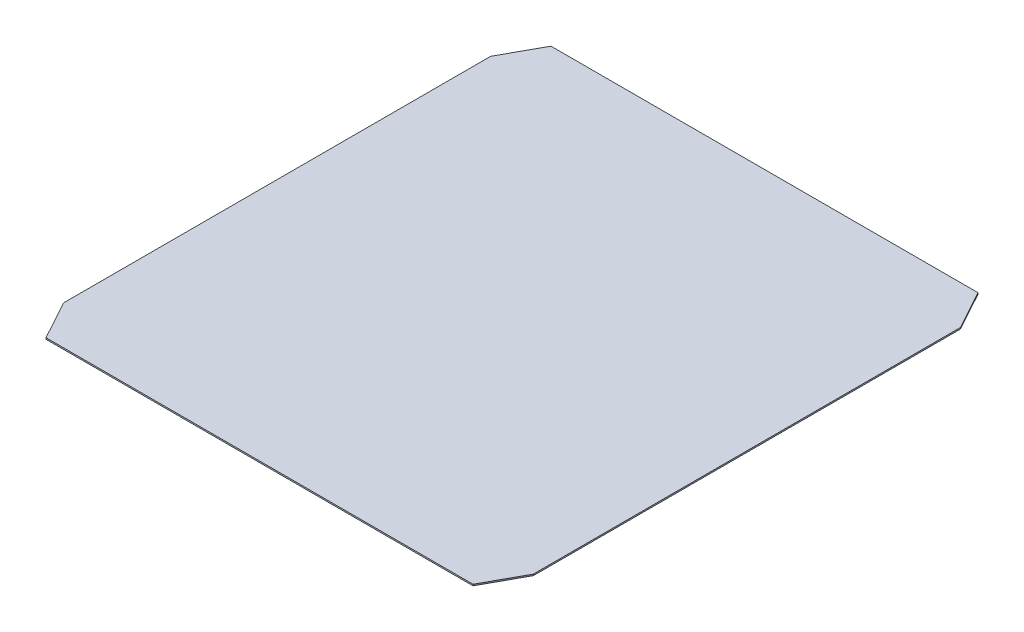
SolidWorks part; units mm, degrees
material "AISI 1020"
ref_plane "Спереди" through (0, 0, 0) normal (0, 0, 1) x (1, 0, 0)
ref_plane "Сверху" through (0, 0, 0) normal (0, 1, 0) x (1, 0, 0)
ref_plane "Справа" through (0, 0, 0) normal (1, 0, 0) x (0, 0, -1)
sketch "Эскиз1" plane through (0, 0, 0) normal (0, 1, 0) x (1, 0, 0)
  line L4 (0, -1000) -> (0, 49000) construction
  line L5 (-1000, 0) -> (49000, 0) construction
  line L6 (-500.5, 455) -> (-455, 538)
  line L7 (500.5, 455) -> (455, 538)
  line L8 (500.5, -538) -> (500.5, 538)
  line L9 (-500.5, -538) -> (500.5, -538)
  line L10 (-500.5, 538) -> (-500.5, -538)
  line L11 (500.5, 538) -> (-500.5, 538)
  line L12 (500.5, -455) -> (500.5, 455)
  line L13 (-455, -538) -> (455, -538)
  line L14 (-500.5, 455) -> (-500.5, -455)
  line L15 (455, 538) -> (-455, 538)
  line L16 (500.5, -455) -> (455, -538)
  line L17 (-500.5, -455) -> (-455, -538)
  dimension "D2" = 5
  dimension "D3" = 5
  dimension "D1" = 2
base flange "Базовая кромка1" sketch "Эскиз1" thickness 3 reverse thickness direction no parameters "D1"=0.75
sketch "Сгиб-Линии1" plane through (0, 0, 0) normal (0, 1, 0) x (1, 0, 0)
sketch "Граничная рамка1" plane through (0, 0, 0) normal (0, 1, 0) x (1, 0, 0)
sheet metal parameters "Листовой металл3" thickness 3 parameters "D1"=0.75
flat pattern "Развертка3" [suppressed]
sketch "Сгиб-Линии2" plane through (0, 0, 0) normal (0, 1, 0) x (1, 0, 0)
sketch "Граничная рамка2" [suppressed] plane through (0, 0, 0) normal (0, 1, 0) x (1, 0, 0)
